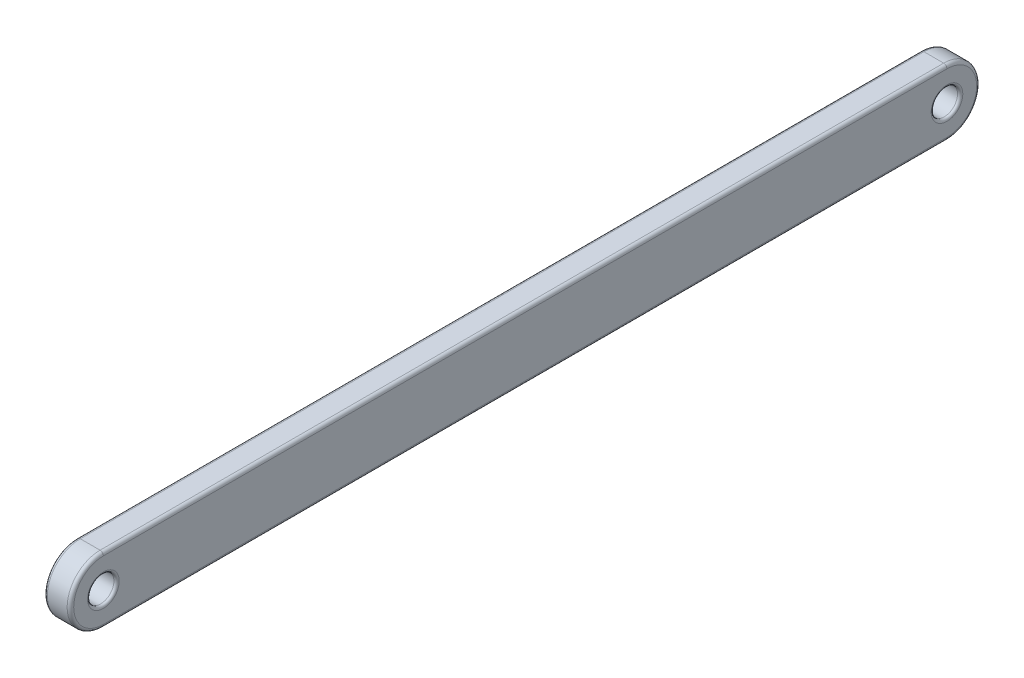
SolidWorks part; units mm, degrees
ref_plane "Front Plane" through (0, 0, 0) normal (0, 0, 1) x (1, 0, 0)
ref_plane "Top Plane" through (0, 0, 0) normal (0, 1, 0) x (1, 0, 0)
ref_plane "Right Plane" through (0, 0, 0) normal (1, 0, 0) x (0, 0, -1)
sketch "Sketch1" plane through (0, 0, 0) normal (1, 0, 0) x (0, 0, -1)
  line L1 (0, 0) -> (30, 0)
  line L2 (0, 0) -> (0, -2.5) construction
  line L3 (0, -2.5) -> (30, -2.5)
  line L4 (30, 0) -> (30, -2.5) construction
  line L5 (0, 0) -> (-1, 0)
  line L6 (0, 0) -> (0, -2.5) construction
  line L7 (0, -2.5) -> (-1, -2.5)
  line L8 (-1, 0) -> (-1, -2.5) construction
  line L9 (30, 0) -> (31, 0)
  line L10 (30, 0) -> (30, -2.5) construction
  line L11 (30, -2.5) -> (31, -2.5)
  line L12 (31, 0) -> (31, -2.5) construction
  line L16 (0, -1.25) -> (-1, -1.25) construction
  line L17 (30, -1.25) -> (31, -1.25) construction
  circle A0 centre (-1, -1.25) radius 0.5
  arc A1 (-1, -2.5) -> (-1, 0) centre (-1, -1.25) cw
  circle A2 centre (31, -1.25) radius 0.5
  arc A3 (31, 0) -> (31, -2.5) centre (31, -1.25) cw
  dimension "D1" = 1
  dimension "D4" = 1
  dimension "D2" = 2.5
  dimension "D3" = 2.5
  dimension "D5" = 32
  dimension "D6" = 2.5
  dimension "D7" = 1
  dimension "D8" = 1
extrude "Boss-Extrude1" add sketch "Sketch1" along normal blind 1 contours A3 L9 L1 L5 A1 L7 L3 L11 A2 A0 region at (0, -1.25, -15)
fillet "Fillet1" radius 0.125 8 edges at (1, -1.25, -32.25) (1, 0, -15) (1, -1.25, 2.25) (0, -1.25, -32.25) (0, 0, -15) (0, -1.25, 2.25) (1, -2.5, -15) (0, -2.5, -15)
fillet "Fillet2" radius 0.1 4 edges at (0, -1.25, -31.5) (1, -1.25, -31.5) (0, -1.25, 0.5) (1, -1.25, 0.5)
